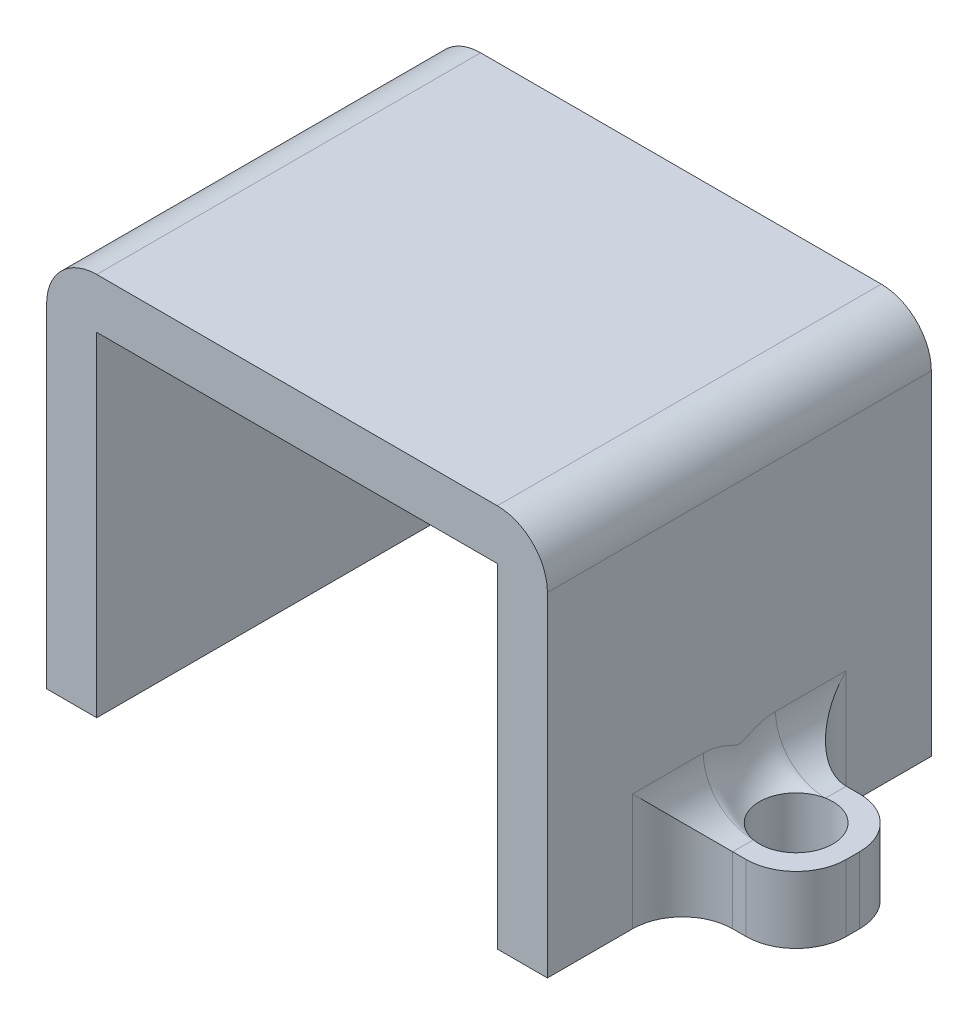
SolidWorks part; units mm, degrees
ref_plane "Alzado" through (0, 0, 0) normal (0, 0, 1) x (1, 0, 0)
ref_plane "Planta" through (0, 0, 0) normal (0, 1, 0) x (1, 0, 0)
ref_plane "Vista lateral" through (0, 0, 0) normal (1, 0, 0) x (0, 0, -1)
sketch "Croquis1" plane through (0, 0, 0) normal (0, 1, 0) x (1, 0, 0)
  line L1 (7.5, -5.75) -> (-7.5, -5.75)
  line L2 (7.5, -5.75) -> (7.5, 5.75)
  line L3 (7.5, 5.75) -> (-7.5, 5.75)
  line L4 (-7.5, -5.75) -> (-7.5, 5.75)
  line L5 (7.5, -5.75) -> (-7.5, 5.75) construction
  line L6 (7.5, 5.75) -> (-7.5, -5.75) construction
  point P0 (0, 0)
  dimension "D1" = 15
  dimension "D2" = 11.5
extrude "Saliente-Extruir1" add sketch "Croquis1" along normal blind 11.5
sketch "Croquis2" plane through (0, 0, 5.75) normal (0, 0, 1) x (1, 0, 0)
  line L0 (7.5, 11.5) -> (7.5, 0) construction
  line L1 (-6, 0) -> (6, 0)
  line L2 (-6, 0) -> (-6, 10)
  line L3 (-6, 10) -> (6, 10)
  line L4 (6, 0) -> (6, 10)
  line L5 (-6, 0) -> (6, 10) construction
  line L6 (-6, 10) -> (6, 0) construction
  line L7 (-7.5, 0) -> (7.5, 0) construction
  line L8 (-7.5, 11.5) -> (-7.5, 0) construction
  point P4 (0, 5)
  dimension "D1" = 12
  dimension "D2" = 10
  dimension "D3" = 1.5
  dimension "D4" = 1.5
extrude "Cortar-Extruir1" cut sketch "Croquis2" against normal up to next
fillet "Redondeo1" radius 1.5 2 edges at (7.5, 11.5, 0) (-7.5, 11.5, 0)
sketch "Croquis3" plane through (0, 0, 0) normal (0, -1, 0) x (1, 0, 0)
  line L0 (-7.5, -5.75) -> (-7.5, 5.75) construction
  line L1 (-7.5, 1.7) -> (-10.9, 1.7)
  line L2 (-7.5, 1.7) -> (-7.5, -1.7)
  line L3 (-7.5, -1.7) -> (-10.9, -1.7)
  line L4 (-10.9, 1.7) -> (-10.9, -1.7)
  line L5 (-7.5, 1.7) -> (-10.9, -1.7) construction
  line L6 (-7.5, -1.7) -> (-10.9, 1.7) construction
  line L8 (-7.5, 5.75) -> (-7.5, -5.75) construction
  line L9 (-7.5, 5.75) -> (-6, 5.75) construction
  line L10 (-6, -5.75) -> (-7.5, -5.75) construction
  line L11 (0, -6.325) -> (0, 6.325) construction
  line L12 (7.5, -1.7) -> (10.9, -1.7)
  line L13 (10.9, 1.7) -> (10.9, -1.7)
  line L14 (7.5, 1.7) -> (10.9, 1.7)
  line L15 (7.5, 1.7) -> (7.5, -1.7)
  circle A0 centre (-9.2, 0) radius 1.1
  circle A1 centre (9.2, 0) radius 1.1
  point P4 (-9.2, 0)
  dimension "D7" = 2.2
  dimension "D1" = 3.4
  dimension "D2" = 3.4
  dimension "D3" = 11.5
  dimension "D4" = 5.75
  dimension "D5" = 4.05
  dimension "D6" = 4.05
extrude "Saliente-Extruir2" add sketch "Croquis3" against normal blind 2
fillet "Redondeo2" radius 1.5 6 edges at (-7.5, 2, 0) (-7.5, 1, -1.7) (-7.5, 1, 1.7) (7.5, 1, 1.7) (7.5, 2, 0) (7.5, 1, -1.7)
fillet "Redondeo3" radius 1.5 4 edges at (-10.9, 1, -1.7) (-10.9, 1, 1.7) (10.9, 1, 1.7) (10.9, 1, -1.7)
